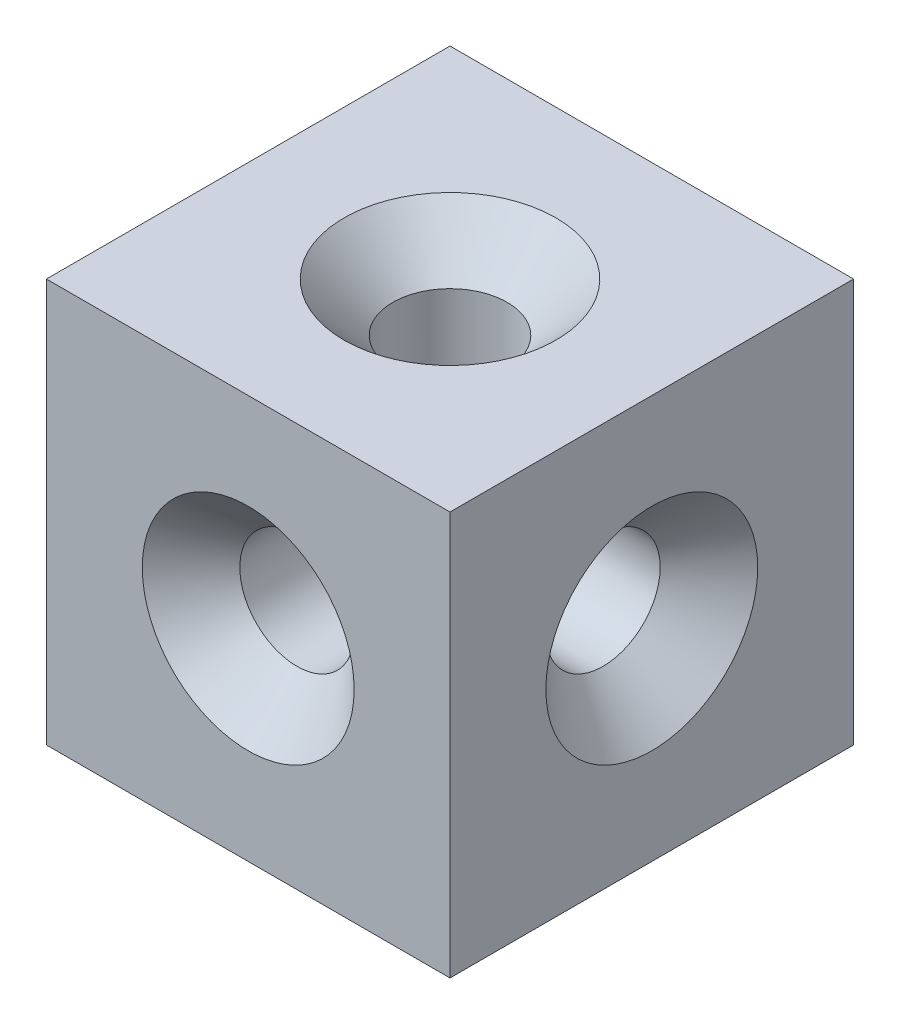
SolidWorks part; units mm, degrees
ref_plane "Front Plane" through (0, 0, 0) normal (0, 0, 1) x (1, 0, 0)
ref_plane "Top Plane" through (0, 0, 0) normal (0, 1, 0) x (1, 0, 0)
ref_plane "Right Plane" through (0, 0, 0) normal (1, 0, 0) x (0, 0, -1)
sketch "Sketch1" plane through (0, 0, 0) normal (0, 0, 1) x (1, 0, 0)
  line L1 (6, -6) -> (-6, -6)
  line L2 (6, -6) -> (6, 6)
  line L3 (6, 6) -> (-6, 6)
  line L4 (-6, -6) -> (-6, 6)
  line L5 (6, -6) -> (-6, 6) construction
  line L6 (6, 6) -> (-6, -6) construction
  point P0 (0, 0)
  dimension "D1" = 12
  dimension "D2" = 12
extrude "Boss-Extrude1" add sketch "Sketch1" along normal mid plane 12
hole_wizard "CSK for M3 Flat Head Machine Screw1" positions "Sketch3" profile "Sketch2" countersink size "M3" standard "ANSI Metric"
sketch "Sketch3" plane through (0, 0, 6) normal (0, 0, 1) x (1, 0, 0)
  point P0 (0, 0)
sketch "Sketch2" plane through (0, 0, 6) normal (1, 0, 0) x (0, -1, 0)
  line L0 (0, 0) -> (0, 7.0215)
  line L1 (0, 7.0215) -> (1.7, 6)
  line L2 (1.7, 6) -> (1.7, 1.45)
  line L3 (1.7, 1.45) -> (3.15, 0)
  line L5 (3.15, 0) -> (0, 0)
  line L6 (-1.7, 1.45) -> (-3.15, 0) construction
  line L10 (0, 7.0215) -> (-1.7, 6) construction
  line L11 (0, -6.35) -> (0, 107.95) construction
  dimension "Hole Dia." = 3.4
  dimension "Hole Depth" = 6
  dimension "Near C'Sink Dia." = 6.3
  dimension "Near C'Sink Angle" = 90
  dimension "Drill Angle" = 118
hole_wizard "CSK for M3 Flat Head Machine Screw2" positions "Sketch6" profile "Sketch7" countersink size "M3" standard "ANSI Metric"
sketch "Sketch6" plane through (6, 0, 0) normal (1, 0, 0) x (0, 0, -1)
  point P0 (0, 0)
sketch "Sketch7" plane through (6, 0, 0) normal (0, 1, 0) x (0, 0, -1)
  line L0 (0, 0) -> (0, 7.0215)
  line L1 (0, 7.0215) -> (1.7, 6)
  line L2 (1.7, 6) -> (1.7, 1.45)
  line L3 (1.7, 1.45) -> (3.15, 0)
  line L5 (3.15, 0) -> (0, 0)
  line L6 (-1.7, 1.45) -> (-3.15, 0) construction
  line L10 (0, 7.0215) -> (-1.7, 6) construction
  line L11 (0, -6.35) -> (0, 107.95) construction
  dimension "Hole Dia." = 3.4
  dimension "Hole Depth" = 6
  dimension "Near C'Sink Dia." = 6.3
  dimension "Near C'Sink Angle" = 90
  dimension "Drill Angle" = 118
hole_wizard "CSK for M3 Flat Head Machine Screw3" positions "Sketch8" profile "Sketch9" countersink size "M3" standard "ANSI Metric"
sketch "Sketch8" plane through (0, 0, -6) normal (0, 0, -1) x (-1, 0, 0)
  point P0 (0, 0)
sketch "Sketch9" plane through (0, 0, -6) normal (1, 0, 0) x (0, 1, 0)
  line L0 (0, 0) -> (0, 7.0215)
  line L1 (0, 7.0215) -> (1.7, 6)
  line L2 (1.7, 6) -> (1.7, 1.45)
  line L3 (1.7, 1.45) -> (3.15, 0)
  line L5 (3.15, 0) -> (0, 0)
  line L6 (-1.7, 1.45) -> (-3.15, 0) construction
  line L10 (0, 7.0215) -> (-1.7, 6) construction
  line L11 (0, -6.35) -> (0, 107.95) construction
  dimension "Hole Dia." = 3.4
  dimension "Hole Depth" = 6
  dimension "Near C'Sink Dia." = 6.3
  dimension "Near C'Sink Angle" = 90
  dimension "Drill Angle" = 118
hole_wizard "CSK for M3 Flat Head Machine Screw7" positions "Sketch10" profile "Sketch11" countersink size "M3" standard "ANSI Metric"
sketch "Sketch10" plane through (-6, 0, 0) normal (-1, 0, 0) x (0, 0, 1)
  point P0 (0, 0)
  point P4 (0, 0)
sketch "Sketch11" plane through (-6, 0, 0) normal (0, 1, 0) x (0, 0, 1)
  line L0 (0, 0) -> (0, 7.0215)
  line L1 (0, 7.0215) -> (1.7, 6)
  line L2 (1.7, 6) -> (1.7, 1.45)
  line L3 (1.7, 1.45) -> (3.15, 0)
  line L5 (3.15, 0) -> (0, 0)
  line L6 (-1.7, 1.45) -> (-3.15, 0) construction
  line L10 (0, 7.0215) -> (-1.7, 6) construction
  line L11 (0, -6.35) -> (0, 107.95) construction
  dimension "Hole Dia." = 3.4
  dimension "Hole Depth" = 6
  dimension "Near C'Sink Dia." = 6.3
  dimension "Near C'Sink Angle" = 90
  dimension "Drill Angle" = 118
hole_wizard "CSK for M3 Flat Head Machine Screw8" positions "Sketch12" profile "Sketch13" countersink size "M3" standard "ANSI Metric"
sketch "Sketch12" plane through (0, 6, 0) normal (0, 1, 0) x (1, 0, 0)
  point P0 (0, 0)
sketch "Sketch13" plane through (0, 6, 0) normal (1, 0, 0) x (0, 0, 1)
  line L0 (0, 0) -> (0, 7.0215)
  line L1 (0, 7.0215) -> (1.7, 6)
  line L2 (1.7, 6) -> (1.7, 1.45)
  line L3 (1.7, 1.45) -> (3.15, 0)
  line L5 (3.15, 0) -> (0, 0)
  line L6 (-1.7, 1.45) -> (-3.15, 0) construction
  line L10 (0, 7.0215) -> (-1.7, 6) construction
  line L11 (0, -6.35) -> (0, 107.95) construction
  dimension "Hole Dia." = 3.4
  dimension "Hole Depth" = 6
  dimension "Near C'Sink Dia." = 6.3
  dimension "Near C'Sink Angle" = 90
  dimension "Drill Angle" = 118
hole_wizard "CSK for M3 Flat Head Machine Screw9" positions "Sketch14" profile "Sketch15" countersink size "M3" standard "ANSI Metric"
sketch "Sketch14" plane through (0, -6, 0) normal (0, -1, 0) x (-1, 0, 0)
  point P0 (0, 0)
sketch "Sketch15" plane through (0, -6, 0) normal (1, 0, 0) x (0, 0, -1)
  line L0 (0, 0) -> (0, 7.0215)
  line L1 (0, 7.0215) -> (1.7, 6)
  line L2 (1.7, 6) -> (1.7, 1.45)
  line L3 (1.7, 1.45) -> (3.15, 0)
  line L5 (3.15, 0) -> (0, 0)
  line L6 (-1.7, 1.45) -> (-3.15, 0) construction
  line L10 (0, 7.0215) -> (-1.7, 6) construction
  line L11 (0, -6.35) -> (0, 107.95) construction
  dimension "Hole Dia." = 3.4
  dimension "Hole Depth" = 6
  dimension "Near C'Sink Dia." = 6.3
  dimension "Near C'Sink Angle" = 90
  dimension "Drill Angle" = 118
equation "\"Length\"= 283mm"
equation "\"Width\"= 225mm"
equation "\"WallThickness\"= 12.5mm"
equation "\"UpperWaterJacketThickness\"= 28mm"
equation "\"SpacerHeight\"= 80.2mm"
equation "\"SpacerCornerWidth\"= 10mm"
equation "\"SpacerCornerHeight\"= 60.16mm"
equation "\"SpacerPegDiameter\"= 10mm"
equation "\"SpacerPegHeight\"= 10mm"
equation "\"TubingShort\"= 110mm"
equation "\"TubingLong\"= 175mm"
equation "\"PlateLength\"= 252mm"
equation "\"PlateWidth\"= 190mm"
equation "\"PlateHoleDiameter\"= 5.9mm"
equation "\"PlateHoleBottom\"= 2mm"
equation "\"PlateHoleSide\"= 1.55mm"
equation "\"PlateHoleSpacing\"= 3.1mm"
equation "\"PlateThickness\"= 1.55mm"
equation "\"ReservoirBottom\"= 12.5mm"
equation "\"ReservoirSupportWidth\"= 12mm"
equation "\"ReservoirSupportHeight\"= 15.1mm"
equation "\"ReservoirSupportPlacementHeight\"= 50mm"
equation "\"ReservoirHoleDiameter\"= 12.7mm"
equation "\"ReservoirHoleRight\"= 25mm"
equation "\"ReservoirHoleTop\"= \"ReservoirSupportPlacementHeight\""
equation "\"ReservoirHeight\"= 90mm"
equation "\"ReservoirPortBottom\"= 4mm"
equation "\"ReservoirPortTop\"= 10mm"
equation "\"ReservoirPortWidth\"= 101mm"
equation "\"CustomSpacerWallThickness\"= 0.375in"
equation "\"CustomSpacerHeight\"= 5in"
equation "\"CustomSpacerRodHoleHeight\"= .75in"
equation "\"CustomSpacerRodHoleDiameter\"= .3125in"
equation "\"ScrewBlockSide\"= 12mm"
equation "\"ScrewBlockUpperHeight\"= 16mm"
equation "\"ScrewBlockLowerHeight\"= 16mm"
equation "\"InternalLength\"= 258mm"
equation "\"InternalWidth\"= 200mm"
equation "\"CustomSpacerPegHeight\"= 1in"
equation "\"CustomSpacerScrewBore\"=3.2mm"
equation "\"CustomSpacerScrewDepth\"=10mm"
equation "\"D1@Sketch1\"=\"ScrewBlockSide\""
equation "\"D2@Sketch1\"=\"ScrewBlockSide\""
equation "\"D1@Boss-Extrude1\"=\"ScrewBlockSide\""
